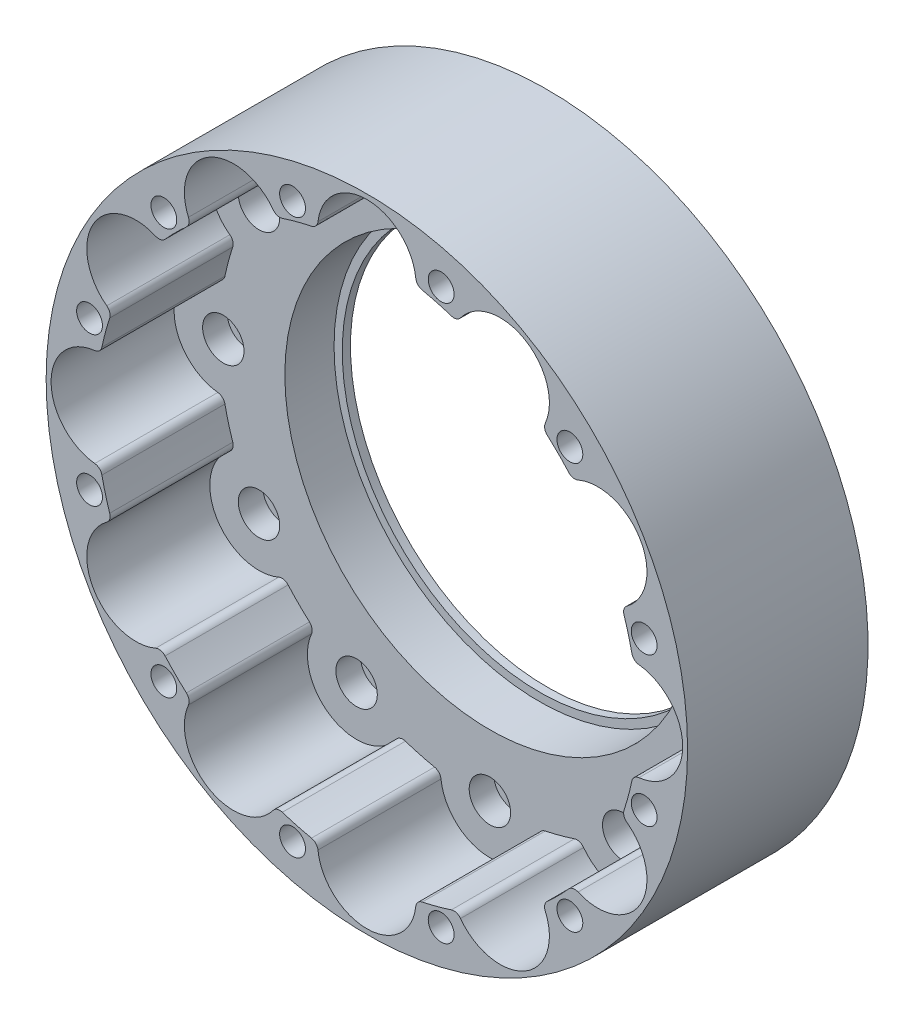
SolidWorks part; units mm, degrees
material "ABS"
ref_plane "Front Plane" through (0, 0, 0) normal (0, 0, 1) x (1, 0, 0)
ref_plane "Top Plane" through (0, 0, 0) normal (0, 1, 0) x (1, 0, 0)
ref_plane "Right Plane" through (0, 0, 0) normal (1, 0, 0) x (0, 0, -1)
sketch "Sketch1" plane through (0, 0, 0) normal (0, 0, 1) x (1, 0, 0)
  circle A0 centre (0, 0) radius 39.1
  circle A1 centre (0, 0) radius 32.5 construction
  circle A2 centre (32.5, 0) radius 2.525
  circle A3 centre (28.1458, -16.25) radius 2.525
  circle A4 centre (16.25, -28.1458) radius 2.525
  circle A5 centre (0, -32.5) radius 2.525
  circle A6 centre (-16.25, -28.1458) radius 2.525
  circle A7 centre (-28.1458, -16.25) radius 2.525
  circle A8 centre (-32.5, 0) radius 2.525
  circle A9 centre (-28.1458, 16.25) radius 2.525
  circle A10 centre (-16.25, 28.1458) radius 2.525
  circle A11 centre (0, 32.5) radius 2.525
  circle A12 centre (16.25, 28.1458) radius 2.525
  circle A13 centre (0, 0) radius 16
  circle A14 centre (28.1458, 16.25) radius 2.525
  point P28 (0, 0)
extrude "Boss-Extrude1" add sketch "Sketch1" along normal blind 3
sketch "Sketch2" plane through (0, 0, 0) normal (0, 0, -1) x (-1, 0, 0)
  circle A0 centre (0, 0) radius 16
  circle A1 centre (0, 0) radius 39.1
  circle A2 centre (0, 0) radius 39.1 construction
  dimension "D1" = 32
extrude "Boss-Extrude2" add sketch "Sketch2" along normal blind 4 contours A1 | A0
sketch "Sketch3" plane through (0, 0, 3) normal (0, 0, 1) x (1, 0, 0)
  circle A0 centre (32.5, 0) radius 1.6
  circle A1 centre (28.1458, -16.25) radius 1.6
  circle A2 centre (16.25, -28.1458) radius 1.6
  circle A3 centre (0, -32.5) radius 1.6
  circle A4 centre (-16.25, -28.1458) radius 1.6
  circle A5 centre (-28.1458, -16.25) radius 1.6
  circle A6 centre (-32.5, 0) radius 1.6
  circle A7 centre (-28.1458, 16.25) radius 1.6
  circle A8 centre (-16.25, 28.1458) radius 1.6
  circle A9 centre (0, 32.5) radius 1.6
  circle A10 centre (16.25, 28.1458) radius 1.6
  circle A11 centre (28.1458, 16.25) radius 1.6
  point P25 (0, 0)
  dimension "D1" = 3.2
  dimension "D2" = 12
sketch "Sketch4" plane through (0, 0, -4) normal (0, 0, -1) x (-1, 0, 0)
  circle A0 centre (0, 0) radius 25
  circle A1 centre (0, 0) radius 24
  circle M15 centre (0, 0) radius 16
  dimension "D1" = 50
  dimension "D2" = 48
sketch "Sketch5" plane through (0, 0, 3) normal (0, 0, 1) x (1, 0, 0)
  circle A0 centre (0, 0) radius 39.1
  circle A1 centre (0, 0) radius 39.1 construction
  arc A2 (-11.029, 31.1024) -> (-21.421, 25.1026) centre (-16.25, 28.1458) ccw
  arc A3 (5.9998, 32.45) -> (-5.9998, 32.45) centre (0, 32.5) ccw
  arc A4 (21.421, 25.1026) -> (11.029, 31.1024) centre (16.25, 28.1458) ccw
  arc A5 (31.1024, 11.029) -> (25.1026, 21.421) centre (28.1458, 16.25) ccw
  arc A6 (32.45, -5.9998) -> (32.45, 5.9998) centre (32.5, 0) ccw
  arc A7 (25.1026, -21.421) -> (31.1024, -11.029) centre (28.1458, -16.25) ccw
  arc A8 (11.029, -31.1024) -> (21.421, -25.1026) centre (16.25, -28.1458) ccw
  arc A9 (-5.9998, -32.45) -> (5.9998, -32.45) centre (0, -32.5) ccw
  arc A10 (-21.421, -25.1026) -> (-11.029, -31.1024) centre (-16.25, -28.1458) ccw
  arc A11 (-31.1024, -11.029) -> (-25.1026, -21.421) centre (-28.1458, -16.25) ccw
  arc A12 (-32.45, 5.9998) -> (-32.45, -5.9998) centre (-32.5, 0) ccw
  arc A13 (-25.1026, -21.421) -> (-21.421, -25.1026) centre (0, 0) ccw
  arc A14 (-32.45, -5.9998) -> (-31.1024, -11.029) centre (0, 0) ccw
  arc A15 (-21.421, 25.1026) -> (-25.1026, 21.421) centre (0, 0) ccw
  arc A16 (-5.9998, 32.45) -> (-11.029, 31.1024) centre (0, 0) ccw
  arc A17 (11.029, 31.1024) -> (5.9998, 32.45) centre (0, 0) ccw
  arc A18 (25.1026, 21.421) -> (21.421, 25.1026) centre (0, 0) ccw
  arc A19 (32.45, 5.9998) -> (31.1024, 11.029) centre (0, 0) ccw
  arc A20 (31.1024, -11.029) -> (32.45, -5.9998) centre (0, 0) ccw
  arc A21 (21.421, -25.1026) -> (25.1026, -21.421) centre (0, 0) ccw
  arc A22 (5.9998, -32.45) -> (11.029, -31.1024) centre (0, 0) ccw
  arc A23 (-11.029, -31.1024) -> (-5.9998, -32.45) centre (0, 0) ccw
  arc A24 (-25.1026, 21.421) -> (-31.1024, 11.029) centre (-28.1458, 16.25) ccw
  arc A25 (-31.1024, 11.029) -> (-32.45, 5.9998) centre (0, 0) ccw
  point P30 (0, 0)
  dimension "D1" = 12
  dimension "D2" = 6
  dimension "D3" = 33
extrude "Boss-Extrude4" add sketch "Sketch5" along normal blind 15 contours A24 A15 A2 A0 | A16 A3 A0 A2 | A17 A4 A0 A3 | A18 A5 A0 A4 | A19 A6 A0 A5 | A20 A7 A0 A6 | A21 A8 A0 A7 | A22 A9 A0 A8 | A23 A10 A0 A9 | A13 A11 A0 A10 | A14 A12 A0 A11 | A24 A0 A12 A15 region at (-38.9894, 0, 3)
fillet "Fillet2" radius 1 24 edges at (11.029, -31.1024, 10.5) (5.9998, -32.45, 10.5) (32.45, -5.9998, 10.5) (31.1024, -11.029, 10.5) (25.1026, -21.421, 10.5) (21.421, -25.1026, 10.5) (-11.029, -31.1024, 10.5) (-5.9998, -32.45, 10.5) (-21.421, -25.1026, 10.5) (-25.1026, -21.421, 10.5) (-32.45, -5.9998, 10.5) (-31.1024, -11.029, 10.5) (-21.421, 25.1026, 10.5) (32.45, 5.9998, 10.5) (31.1024, 11.029, 10.5) (25.1026, 21.421, 10.5) (21.421, 25.1026, 10.5) (11.029, 31.1024, 10.5) (5.9998, 32.45, 10.5) (-5.9998, 32.45, 10.5) (-11.029, 31.1024, 10.5) (-32.45, 5.9998, 10.5) (-31.1024, 11.029, 10.5) (-25.1026, 21.421, 10.5)
sketch "Sketch7" plane through (0, 0, -4) normal (0, 0, -1) x (-1, 0, 0)
  line L0 (0, 0) -> (33.8074, -9.0587) construction
  line L1 (0, 0) -> (35, 0) construction
  circle A0 centre (33.8074, -9.0587) radius 1.575
  circle A1 centre (24.7487, -24.7487) radius 1.575
  circle A2 centre (9.0587, -33.8074) radius 1.575
  circle A3 centre (-9.0587, -33.8074) radius 1.575
  circle A4 centre (-24.7487, -24.7487) radius 1.575
  circle A5 centre (-33.8074, -9.0587) radius 1.575
  circle A6 centre (-33.8074, 9.0587) radius 1.575
  circle A7 centre (-24.7487, 24.7487) radius 1.575
  circle A8 centre (-9.0587, 33.8074) radius 1.575
  circle A9 centre (9.0587, 33.8074) radius 1.575
  circle A10 centre (24.7487, 24.7487) radius 1.575
  circle A11 centre (33.8074, 9.0587) radius 1.575
  point P26 (0, 0)
  dimension "D2" = 3.15
  dimension "D4" = 35
  dimension "D5" = 15
  dimension "D3" = 12
extrude "Cut-Extrude1" cut sketch "Sketch7" against normal through all
sketch "Sketch8" plane through (0, 0, -4) normal (0, 0, -1) x (-1, 0, 0)
  line L0 (27.5987, -26.3942) -> (27.5987, -23.1033)
  line L1 (37.0983, -9.0587) -> (35.4529, -6.2087)
  line L2 (35.4529, -6.2087) -> (32.162, -6.2087)
  line L3 (32.162, -6.2087) -> (30.5165, -9.0587)
  line L4 (30.5165, -9.0587) -> (32.162, -11.9087)
  line L5 (32.162, -11.9087) -> (35.4529, -11.9087)
  line L6 (35.4529, -11.9087) -> (37.0983, -9.0587)
  line L7 (27.5987, -23.1033) -> (24.7487, -21.4578)
  line L8 (24.7487, -21.4578) -> (21.8987, -23.1033)
  line L9 (21.8987, -23.1033) -> (21.8987, -26.3942)
  line L10 (21.8987, -26.3942) -> (24.7487, -28.0396)
  line L11 (24.7487, -28.0396) -> (27.5987, -26.3942)
  line L12 (10.7041, -36.6574) -> (12.3496, -33.8074)
  line L13 (12.3496, -33.8074) -> (10.7041, -30.9574)
  line L14 (10.7041, -30.9574) -> (7.4132, -30.9574)
  line L15 (7.4132, -30.9574) -> (5.7678, -33.8074)
  line L16 (5.7678, -33.8074) -> (7.4132, -36.6574)
  line L17 (7.4132, -36.6574) -> (10.7041, -36.6574)
  line L18 (-9.0587, -37.0983) -> (-6.2087, -35.4529)
  line L19 (-6.2087, -35.4529) -> (-6.2087, -32.162)
  line L20 (-6.2087, -32.162) -> (-9.0587, -30.5165)
  line L21 (-9.0587, -30.5165) -> (-11.9087, -32.162)
  line L22 (-11.9087, -32.162) -> (-11.9087, -35.4529)
  line L23 (-11.9087, -35.4529) -> (-9.0587, -37.0983)
  line L24 (-26.3942, -27.5987) -> (-23.1033, -27.5987)
  line L25 (-23.1033, -27.5987) -> (-21.4578, -24.7487)
  line L26 (-21.4578, -24.7487) -> (-23.1033, -21.8987)
  line L27 (-23.1033, -21.8987) -> (-26.3942, -21.8987)
  line L28 (-26.3942, -21.8987) -> (-28.0396, -24.7487)
  line L29 (-28.0396, -24.7487) -> (-26.3942, -27.5987)
  line L30 (-36.6574, -10.7041) -> (-33.8074, -12.3496)
  line L31 (-33.8074, -12.3496) -> (-30.9574, -10.7041)
  line L32 (-30.9574, -10.7041) -> (-30.9574, -7.4132)
  line L33 (-30.9574, -7.4132) -> (-33.8074, -5.7678)
  line L34 (-33.8074, -5.7678) -> (-36.6574, -7.4132)
  line L35 (-36.6574, -7.4132) -> (-36.6574, -10.7041)
  line L36 (-37.0983, 9.0587) -> (-35.4529, 6.2087)
  line L37 (-35.4529, 6.2087) -> (-32.162, 6.2087)
  line L38 (-32.162, 6.2087) -> (-30.5165, 9.0587)
  line L39 (-30.5165, 9.0587) -> (-32.162, 11.9087)
  line L40 (-32.162, 11.9087) -> (-35.4529, 11.9087)
  line L41 (-35.4529, 11.9087) -> (-37.0983, 9.0587)
  line L42 (-27.5987, 26.3942) -> (-27.5987, 23.1033)
  line L43 (-27.5987, 23.1033) -> (-24.7487, 21.4578)
  line L44 (-24.7487, 21.4578) -> (-21.8987, 23.1033)
  line L45 (-21.8987, 23.1033) -> (-21.8987, 26.3942)
  line L46 (-21.8987, 26.3942) -> (-24.7487, 28.0396)
  line L47 (-24.7487, 28.0396) -> (-27.5987, 26.3942)
  line L48 (-10.7041, 36.6574) -> (-12.3496, 33.8074)
  line L49 (-12.3496, 33.8074) -> (-10.7041, 30.9574)
  line L50 (-10.7041, 30.9574) -> (-7.4132, 30.9574)
  line L51 (-7.4132, 30.9574) -> (-5.7678, 33.8074)
  line L52 (-5.7678, 33.8074) -> (-7.4132, 36.6574)
  line L53 (-7.4132, 36.6574) -> (-10.7041, 36.6574)
  line L54 (9.0587, 37.0983) -> (6.2087, 35.4529)
  line L55 (6.2087, 35.4529) -> (6.2087, 32.162)
  line L56 (6.2087, 32.162) -> (9.0587, 30.5165)
  line L57 (9.0587, 30.5165) -> (11.9087, 32.162)
  line L58 (11.9087, 32.162) -> (11.9087, 35.4529)
  line L59 (11.9087, 35.4529) -> (9.0587, 37.0983)
  line L60 (26.3942, 27.5987) -> (23.1033, 27.5987)
  line L61 (23.1033, 27.5987) -> (21.4578, 24.7487)
  line L62 (21.4578, 24.7487) -> (23.1033, 21.8987)
  line L63 (23.1033, 21.8987) -> (26.3942, 21.8987)
  line L64 (26.3942, 21.8987) -> (28.0396, 24.7487)
  line L65 (28.0396, 24.7487) -> (26.3942, 27.5987)
  line L66 (36.6574, 10.7041) -> (33.8074, 12.3496)
  line L67 (33.8074, 12.3496) -> (30.9574, 10.7041)
  line L68 (30.9574, 10.7041) -> (30.9574, 7.4132)
  line L69 (30.9574, 7.4132) -> (33.8074, 5.7678)
  line L70 (33.8074, 5.7678) -> (36.6574, 7.4132)
  line L71 (36.6574, 7.4132) -> (36.6574, 10.7041)
  circle A0 centre (33.8074, -9.0587) radius 2.85 construction
  circle A1 centre (24.7487, -24.7487) radius 2.85 construction
  circle A2 centre (9.0587, -33.8074) radius 2.85 construction
  circle A3 centre (-9.0587, -33.8074) radius 2.85 construction
  circle A4 centre (-24.7487, -24.7487) radius 2.85 construction
  circle A5 centre (-33.8074, -9.0587) radius 2.85 construction
  circle A6 centre (-33.8074, 9.0587) radius 2.85 construction
  circle A7 centre (-24.7487, 24.7487) radius 2.85 construction
  circle A8 centre (-9.0587, 33.8074) radius 2.85 construction
  circle A9 centre (9.0587, 33.8074) radius 2.85 construction
  circle A10 centre (24.7487, 24.7487) radius 2.85 construction
  circle A11 centre (33.8074, 9.0587) radius 2.85 construction
  point P91 (0, 0)
  dimension "D1" = 5.7
  dimension "D2" = 12
extrude "Cut-Extrude3" cut sketch "Sketch8" against normal blind 3
sketch "Sketch9" plane through (0, 0, 3) normal (0, 0, 1) x (1, 0, 0)
  circle A0 centre (0, 0) radius 39.1
  circle A1 centre (0, 0) radius 38.5
  dimension "D1" = 77
extrude "Cut-Extrude7" cut sketch "Sketch4" along normal blind 6 from surface contours A0 starting at face at (0, 0, 3)
extrude "Cut-Extrude9" cut sketch "Sketch4<5>" along direction (0, 0, 1) on the side of the normal through all from surface contours A1 M15 region at (23.3212, 0, -4) starting at face at (25, 0, 3)
sketch "Sketch4<5>" plane through (0, 0, -4) normal (0, 0, -1) x (-1, 0, 0) same geometry as "Sketch4"
equation "\"RingPinShaft\"= 5.05"
equation "\"CenterBearingOut\"=32.00"
equation "\"OutputBearingOut\"=50.00"
equation "\"RingPostIn\"=5.15"
equation "\"CamBearingOut\"=15.1"
equation "\"DiskOutputShaft\"=10.1"
equation "\"CenterShaft\"=25.2"
equation "\"Eccentricity\"=2"
equation "\"CycCamShaft\"=10.05"
equation "\"m3Thru\"=3.15"
equation "\"m3Insert\"=4.2"
equation "\"MountingHoleDiam\"=35"
equation "\"D2@Sketch7\"=\"m3Thru\""
equation "\"D4@Sketch7\"=\"MountingHoleDiam\""
